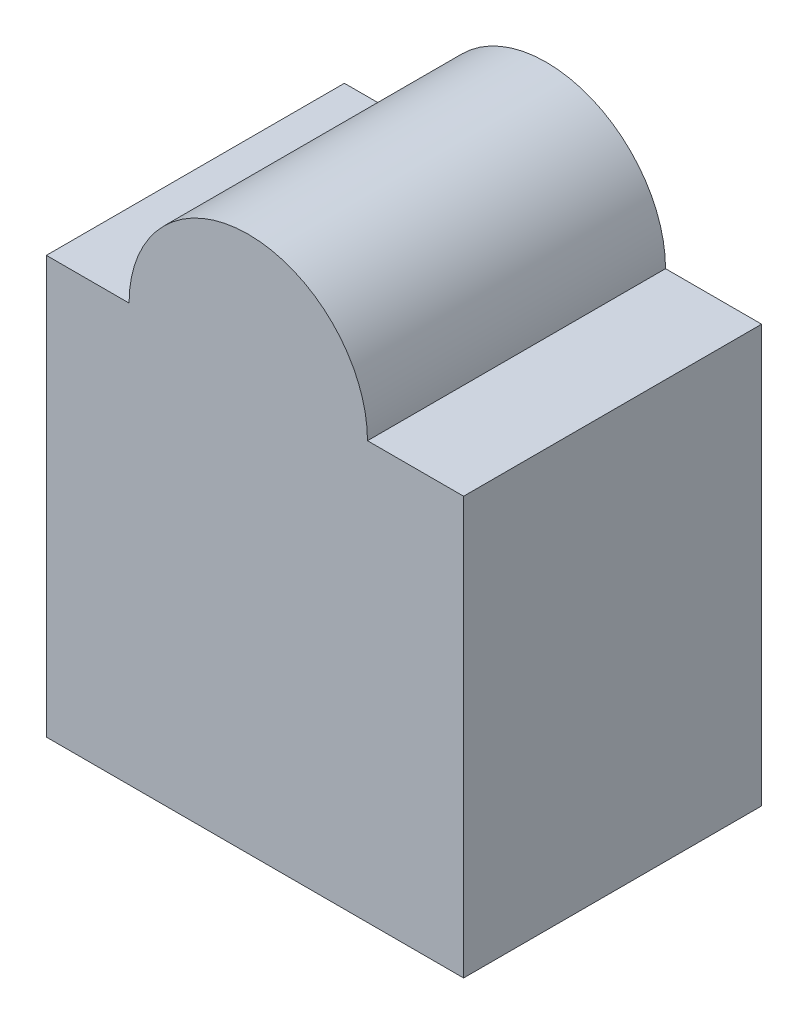
SolidWorks part; units mm, degrees
ref_plane "Plan de face" through (0, 0, 0) normal (0, 0, 1) x (1, 0, 0)
ref_plane "Plan de dessus" through (0, 0, 0) normal (0, 1, 0) x (1, 0, 0)
ref_plane "Plan de droite" through (0, 0, 0) normal (1, 0, 0) x (0, 0, -1)
sketch "Esquisse1" plane through (0, 0, 0) normal (0, 0, 1) x (1, 0, 0)
  line L0 (0, 0) -> (700, 0)
  line L1 (700, 0) -> (700, 450)
  line L2 (700, 450) -> (538.7581, 450)
  line L3 (0, 0) -> (0, 450)
  line L4 (0, 450) -> (138.7581, 450)
  arc A0 (538.7581, 450) -> (138.7581, 450) centre (338.7581, 450) ccw
  dimension "D3" = 200
  dimension "D1" = 700
  dimension "D2" = 450
extrude "Boss.-Extru.1" add sketch "Esquisse1" along normal blind 500
sketch "Esquisse2" plane through (0, 0, 0) normal (0, -1, 0) x (1, 0, 0)
  line L0 (700, 500) -> (700, 0)
  line L1 (700, 0) -> (0, 0)
  line L2 (0, 0) -> (0, 500)
  line L3 (0, 500) -> (700, 500) construction
  line L4 (0, 500) -> (0, 0) construction
  line L5 (0, 500) -> (700, 500)
extrude "Boss.-Extru.2" add sketch "Esquisse2" along normal blind 250
